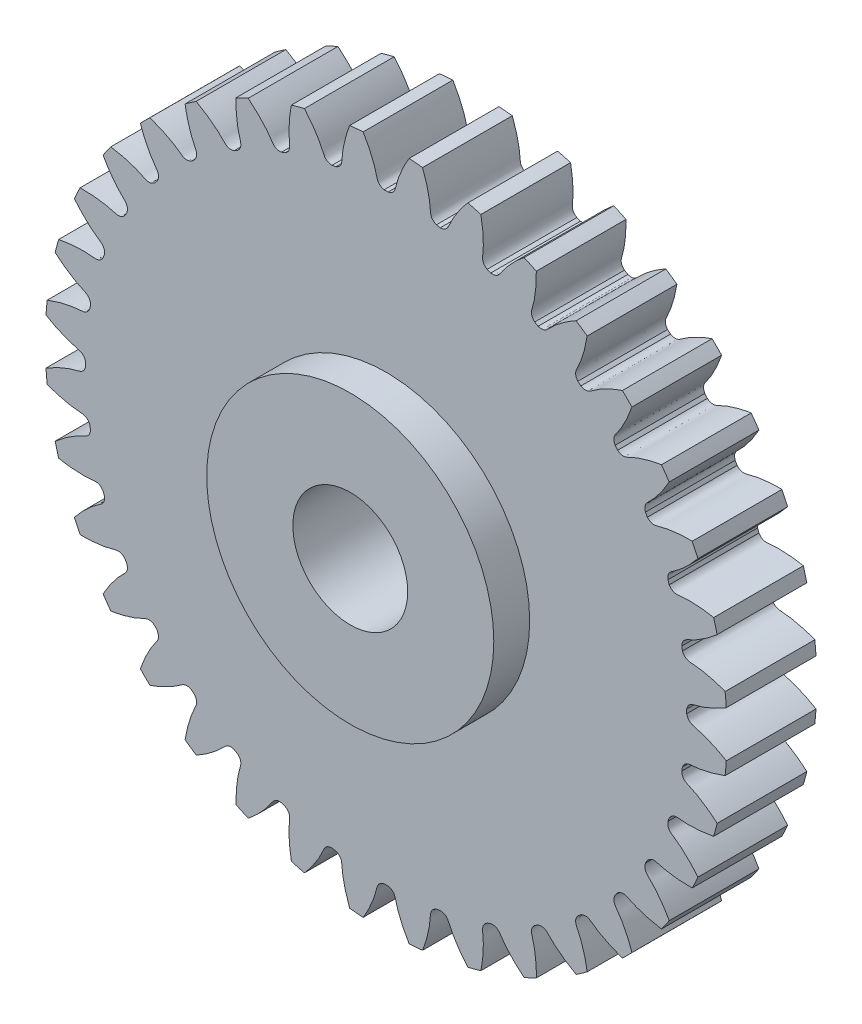
SolidWorks part; units mm, degrees
ref_plane "前视基准面" through (0, 0, 0) normal (0, 0, 1) x (1, 0, 0)
ref_plane "上视基准面" through (0, 0, 0) normal (0, 1, 0) x (1, 0, 0)
ref_plane "右视基准面" through (0, 0, 0) normal (1, 0, 0) x (0, 0, -1)
other "Configuration Table"
sketch "草图1" plane through (0, 0, 0) normal (0, 0, 1) x (1, 0, 0)
  circle A0 centre (0, 0) radius 9.5
extrude "凸台-拉伸1" add sketch "草图1" along normal blind 2.5
ref_axis "基准轴1" through (0, 0, 2.5) along (0, 0, -1)
sketch "草图2" plane through (0, 0, 0) normal (0, 0, 1) x (1, 0, 0)
  line L0 (0, 0) -> (0, 9.5) construction
  circle A0 centre (0, 0) radius 9.5 construction
  arc A1 (0.0549, 8.3748) -> (-0.0549, 8.3748) centre (0, 0) ccw
  arc A2 (1.757, 10.7884) -> (-1.757, 10.7884) centre (0, 0) ccw
  spline S0 degree 3 poles (0.0549, 8.3748) (0.235, 8.4152) (0.2505, 8.5493) (0.2882, 8.6914) (0.2997, 8.7319) (0.3131, 8.7753) (0.3284, 8.8217) (0.3457, 8.871) (0.3652, 8.9231) (0.3869, 8.9779) (0.4111, 9.0354) (0.4378, 9.0956) (0.4671, 9.1582) (0.4992, 9.2232) (0.5341, 9.2907) (0.5719, 9.3603) (0.6128, 9.4322) (0.6569, 9.5061) (0.7043, 9.582) (0.755, 9.6598) (0.8091, 9.7393) (0.8668, 9.8205) (0.9281, 9.9032) (0.9931, 9.9874) (1.0619, 10.0729) (1.1346, 10.1596) (1.2112, 10.2474) (1.2919, 10.3361) (1.3766, 10.4256) (1.4655, 10.5159) (1.5912, 10.6386) (1.6895, 10.7288) (1.757, 10.7884) knots 0 0 0 0 0.120371 0.133303 0.147364 0.162556 0.178878 0.19633 0.214913 0.234626 0.255469 0.277443 0.300547 0.324782 0.350146 0.376641 0.404267 0.433023 0.462909 0.493925 0.526072 0.559349 0.593757 0.629294 0.665963 0.703761 0.74269 0.782749 0.823939 0.866258 0.909709 1 1 1 1
  spline S1 degree 3 poles (-0.0549, 8.3748) (-0.235, 8.4152) (-0.2505, 8.5493) (-0.2882, 8.6914) (-0.2997, 8.7319) (-0.3131, 8.7753) (-0.3284, 8.8217) (-0.3457, 8.871) (-0.3652, 8.9231) (-0.3869, 8.9779) (-0.4111, 9.0354) (-0.4378, 9.0956) (-0.4671, 9.1582) (-0.4992, 9.2232) (-0.5341, 9.2907) (-0.5719, 9.3603) (-0.6128, 9.4322) (-0.6569, 9.5061) (-0.7043, 9.582) (-0.755, 9.6598) (-0.8091, 9.7393) (-0.8668, 9.8205) (-0.9281, 9.9032) (-0.9931, 9.9874) (-1.0619, 10.0729) (-1.1346, 10.1596) (-1.2112, 10.2474) (-1.2919, 10.3361) (-1.3766, 10.4256) (-1.4655, 10.5159) (-1.5912, 10.6386) (-1.6895, 10.7288) (-1.757, 10.7884) knots 0 0 0 0 0.120371 0.133303 0.147364 0.162556 0.178878 0.19633 0.214913 0.234626 0.255469 0.277443 0.300547 0.324782 0.350146 0.376641 0.404267 0.433023 0.462909 0.493925 0.526072 0.559349 0.593757 0.629294 0.665963 0.703761 0.74269 0.782749 0.823939 0.866258 0.909709 1 1 1 1
extrude "切除-拉伸1" cut sketch "草图2" along normal through all
pattern_circular "阵列(圆周)1" count 36 every 10 about axis through (0, 0, 2.5) along (0, 0, -1) of "切除-拉伸1"
sketch "草图3" plane through (0, 0, 0) normal (0, 0, 1) x (1, 0, 0)
  circle A0 centre (0, 0) radius 9 construction
  dimension "Dn" = 18
sketch "草图4" plane through (0, 0, 0) normal (0, 0, -1) x (-1, 0, 0)
  circle A0 centre (0, 0) radius 4
  dimension "D1" = 8
extrude "凸台-拉伸2" add sketch "草图4" against normal offset from surface (3.5 mm away) 1 up to face at (0, 0, 2.5) offset beyond the face yes
sketch "草图5" plane through (0, 0, 3.5) normal (0, 0, 1) x (1, 0, 0)
  circle A0 centre (0, 0) radius 1.6
  dimension "D1" = 3.2
extrude "切除-拉伸2" cut sketch "草图5" against normal up to next
